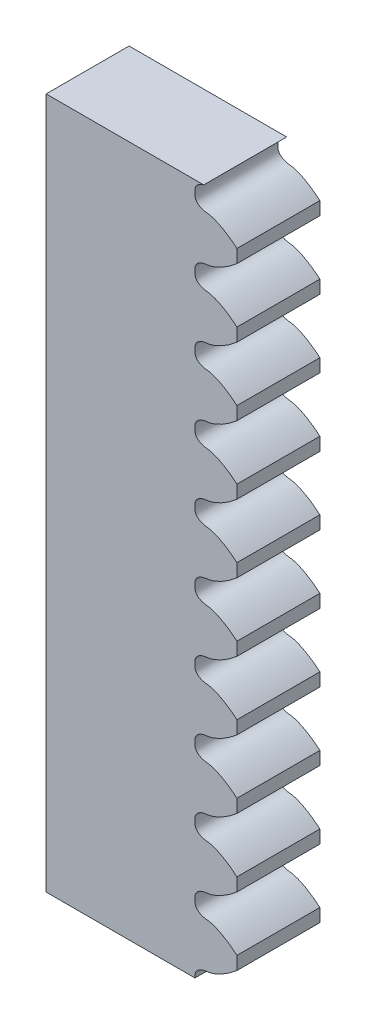
SolidWorks part; units mm, degrees
material "Д16 ГОСТ 4784-97"
ref_plane "FRONT" through (0, 0, 0) normal (0, 0, 1) x (1, 0, 0)
ref_plane "TOP" through (0, 0, 0) normal (0, 1, 0) x (1, 0, 0)
ref_plane "RIGHT" through (0, 0, 0) normal (1, 0, 0) x (0, 0, -1)
ref_axis "Ось1" through (0, 0, 50) along (0, 0, -1)
sketch "Эскиз1" plane through (0, 0, 0) normal (0, 1, 0) x (1, 0, 0)
  line L1 (0, -6) -> (13.8, -6)
  line L2 (0, -6) -> (0, 0)
  line L3 (0, 0) -> (13.8, 0)
  line L4 (13.8, -6) -> (13.8, 0)
  dimension "D1" = 13.8
  dimension "D2" = 6
extrude "Бобышка-Вытянуть1" add sketch "Эскиз1" along normal blind 50
sketch "AuxiliarySketchSpurPinion" plane through (0, 0, 0) normal (0, 0, 1) x (1, 0, 0)
  line L0 (10.7639, 0) -> (10.7639, 60.1957) construction
  line L1 (11.7462, 0) -> (11.7462, 58.1849) construction
  line L2 (12.5, 0) -> (12.5, 55.1708) construction
  line L3 (13.8889, 0) -> (13.8889, 54.0279) construction
  dimension "D1" = 10.7639
  dimension "D2" = 11.7462
  dimension "D3" = 12.5
  dimension "D4" = 13.8889
sketch "SketchToothSpurPinion" plane through (0, 0, 6) normal (0, 0, 1) x (1, 0, 0)
  arc A0 (13.8146, 1.9979) -> (13.8146, -1.9979) centre (0, 0) cw
  spline S0 degree 3 poles (13.8146, -1.9979) (13.6988, -1.8974) (13.5252, -1.7559) (13.2912, -1.5837) (13.1267, -1.4705) (12.9688, -1.3692) (12.8181, -1.2792) (12.6752, -1.2) (12.5406, -1.1309) (12.4148, -1.0713) (12.2982, -1.0206) (12.1913, -0.9782) (12.0946, -0.9433) (12.0082, -0.9152) (11.9327, -0.8933) (11.8682, -0.8768) (11.815, -0.865) (11.7734, -0.8571) (11.7435, -0.8525) (11.7255, -0.8501) (11.69, -0.8469) (11.6475, -0.8436) (11.5944, -0.837) (11.5561, -0.8316) (11.5185, -0.8255) (11.4816, -0.8187) (11.4454, -0.8112) (11.4099, -0.803) (11.375, -0.794) (11.3408, -0.7844) (11.3072, -0.7739) (11.2742, -0.7626) (11.2418, -0.7505) (11.2099, -0.7375) (11.1786, -0.7236) (11.1477, -0.7087) (11.1174, -0.6927) (11.0876, -0.6755) (11.0582, -0.657) (11.0293, -0.637) (11.0009, -0.6155) (10.9731, -0.5923) (10.9459, -0.5672) (10.9194, -0.5399) (10.8939, -0.5103) (10.8695, -0.4783) (10.8465, -0.4436) (10.8254, -0.4061) (10.8065, -0.3659) (10.7903, -0.323) (10.7775, -0.2777) (10.7683, -0.2304) (10.7638, -0.1856) (10.7619, -0.1086) (10.7655, 0) (10.7619, 0.1086) (10.7638, 0.1856) (10.7683, 0.2304) (10.7775, 0.2777) (10.7903, 0.323) (10.8065, 0.3659) (10.8254, 0.4061) (10.8465, 0.4436) (10.8695, 0.4783) (10.8939, 0.5103) (10.9194, 0.5399) (10.9459, 0.5672) (10.9731, 0.5923) (11.0009, 0.6155) (11.0293, 0.637) (11.0582, 0.657) (11.0876, 0.6755) (11.1174, 0.6927) (11.1477, 0.7087) (11.1786, 0.7236) (11.2099, 0.7375) (11.2418, 0.7505) (11.2742, 0.7626) (11.3072, 0.7739) (11.3408, 0.7844) (11.375, 0.794) (11.4099, 0.803) (11.4454, 0.8112) (11.4816, 0.8187) (11.5185, 0.8255) (11.5561, 0.8316) (11.5944, 0.837) (11.6475, 0.8436) (11.69, 0.8469) (11.7255, 0.8501) (11.7435, 0.8525) (11.7734, 0.8571) (11.815, 0.865) (11.8682, 0.8768) (11.9327, 0.8933) (12.0082, 0.9152) (12.0946, 0.9433) (12.1913, 0.9782) (12.2982, 1.0206) (12.4148, 1.0713) (12.5406, 1.1309) (12.6752, 1.2) (12.8181, 1.2792) (12.9688, 1.3692) (13.1267, 1.4705) (13.2912, 1.5837) (13.5252, 1.7559) (13.6988, 1.8974) (13.8146, 1.9979) knots 0 0 0 0 0.059354 0.086688 0.11246 0.136671 0.159319 0.180405 0.19993 0.217892 0.234292 0.249131 0.262408 0.274122 0.284275 0.292866 0.299894 0.305361 0.309266 0.311609 0.31239 0.323048 0.32812 0.333111 0.338025 0.342864 0.347633 0.352337 0.35698 0.361569 0.366108 0.370606 0.375069 0.379506 0.383927 0.388343 0.392764 0.397204 0.401677 0.406198 0.410786 0.415456 0.420229 0.425124 0.430158 0.435351 0.440716 0.446263 0.451995 0.457908 0.463986 0.470203 0.476523 0.481419 0.5 0.518581 0.523477 0.529797 0.536014 0.542092 0.548005 0.553737 0.559284 0.564649 0.569842 0.574876 0.579771 0.584544 0.589214 0.593802 0.598323 0.602796 0.607236 0.611657 0.616073 0.620494 0.624931 0.629394 0.633892 0.638431 0.64302 0.647663 0.652367 0.657136 0.661975 0.666889 0.67188 0.676952 0.68761 0.688391 0.690734 0.694639 0.700106 0.707134 0.715725 0.725878 0.737592 0.750869 0.765708 0.782108 0.80007 0.819595 0.840681 0.863329 0.88754 0.913312 0.940646 1 1 1 1
extrude "ToothExtrudeCutSpurPinion" cut sketch "SketchToothSpurPinion" against normal through all and the other way blind 9.525
pattern_linear "Линейный массив8" count 13 spacing 4.92 along (0, 1, 0) of "ToothExtrudeCutSpurPinion"
